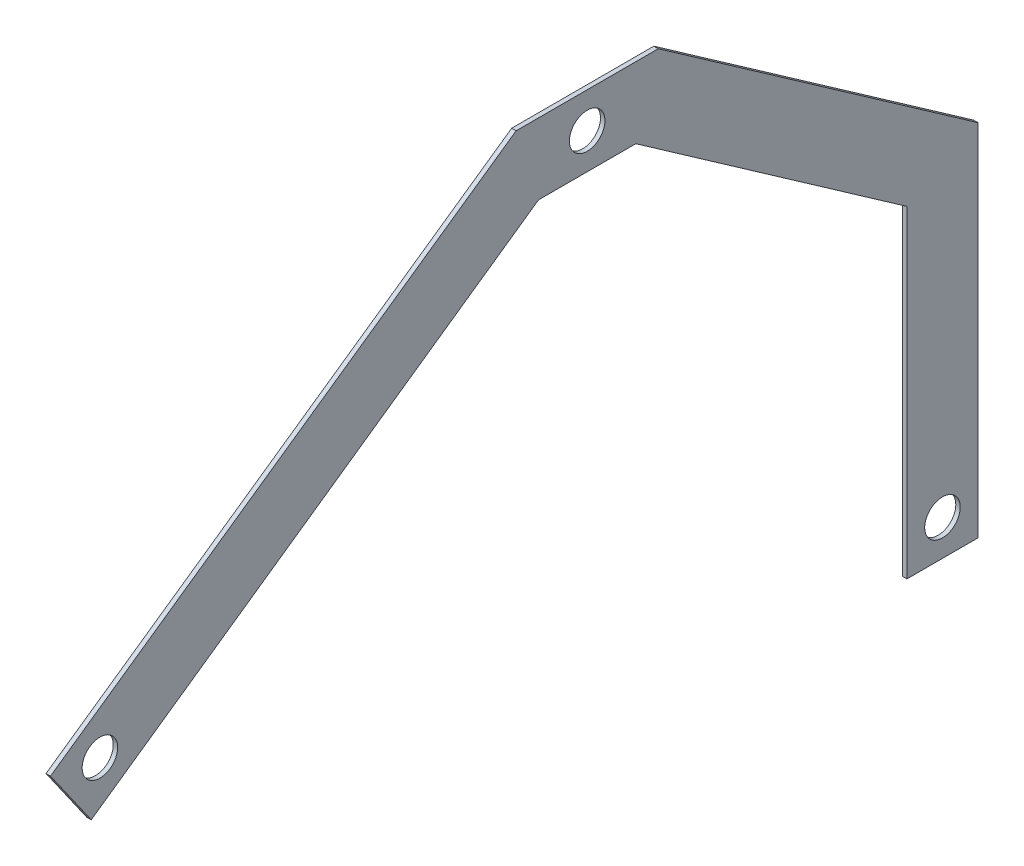
SolidWorks part; units mm, degrees
material "6063-O"
ref_plane "Front" through (0, 0, 0) normal (0, 0, 1) x (1, 0, 0)
ref_plane "Top" through (0, 0, 0) normal (0, 1, 0) x (1, 0, 0)
ref_plane "Right" through (0, 0, 0) normal (1, 0, 0) x (0, 0, -1)
sketch "Sketch1" plane through (0, 0, 0) normal (1, 0, 0) x (0, 0, -1)
  line L0 (-50.8, 25.4) -> (50.8, 25.4)
  line L3 (228.6, -161.1122) -> (34.7828, -25.4)
  line L4 (34.7828, -25.4) -> (-34.7828, -25.4)
  line L5 (-34.7828, -25.4) -> (-354.5657, -249.3144)
  line L6 (-354.5657, -249.3144) -> (-383.7034, -207.7015)
  line L7 (-383.7034, -207.7015) -> (-50.8, 25.4)
  line L8 (0, 25.4) -> (0, -25.4) construction
  line L9 (-278.5961, -165.1122) -> (-41236.1091, -28843.8715) construction
  line L13 (518.6127, -213.9391) -> (-49481.3873, -213.9391) construction
  line L14 (-147.7421, -347.18) -> (49852.2579, -347.18) construction
  line L15 (279.4, -134.6674) -> (279.4, -391.7391)
  line L16 (279.4, -391.7391) -> (228.6, -391.7391)
  line L17 (228.6, -391.7391) -> (228.6, -161.1122)
  line L18 (50.8, 25.4) -> (279.4, -134.6674)
  circle A0 centre (-348.3281, -213.9391) radius 12.7
  circle A1 centre (0, 0) radius 12.7
  point P10 (0, 0)
  point P12 (337.5538, -175.3872)
  point P16 (-369.1345, -228.5079)
  point P23 (279.4, -135.7651)
  point P24 (254, -391.7391)
  point P27 (228.6, -161.1122)
  point P29 (0, 0)
  dimension "D8" = 25.4
  dimension "D1" = 50.8
  dimension "D2" = 50.8
  dimension "D3" = 254
  dimension "D4" = 177.8
  dimension "D5" = 406.4
  dimension "D6" = 145
  dimension "D7" = 101.6
  dimension "D9" = 25.4
  dimension "D10" = 50.8
  dimension "D11" = 347.18
  dimension "D13" = 50.8
extrude "Boss-Extrude1" add sketch "Sketch1" along normal blind 3.175
sketch "Sketch3" plane through (3.175, 0, 0) normal (1, 0, 0) x (0, 0, -1)
  line L0 (254, -391.7391) -> (254, -116.8822) construction
  line L1 (228.6, -391.7391) -> (279.4, -391.7391) construction
  line L2 (279.4, -134.6674) -> (50.8, 25.4) construction
  circle A0 centre (254, -366.3391) radius 12.7
  dimension "D1" = 25.4
  dimension "D2" = 25.4
extrude "Cut-Extrude2" cut sketch "Sketch3" against normal through all
